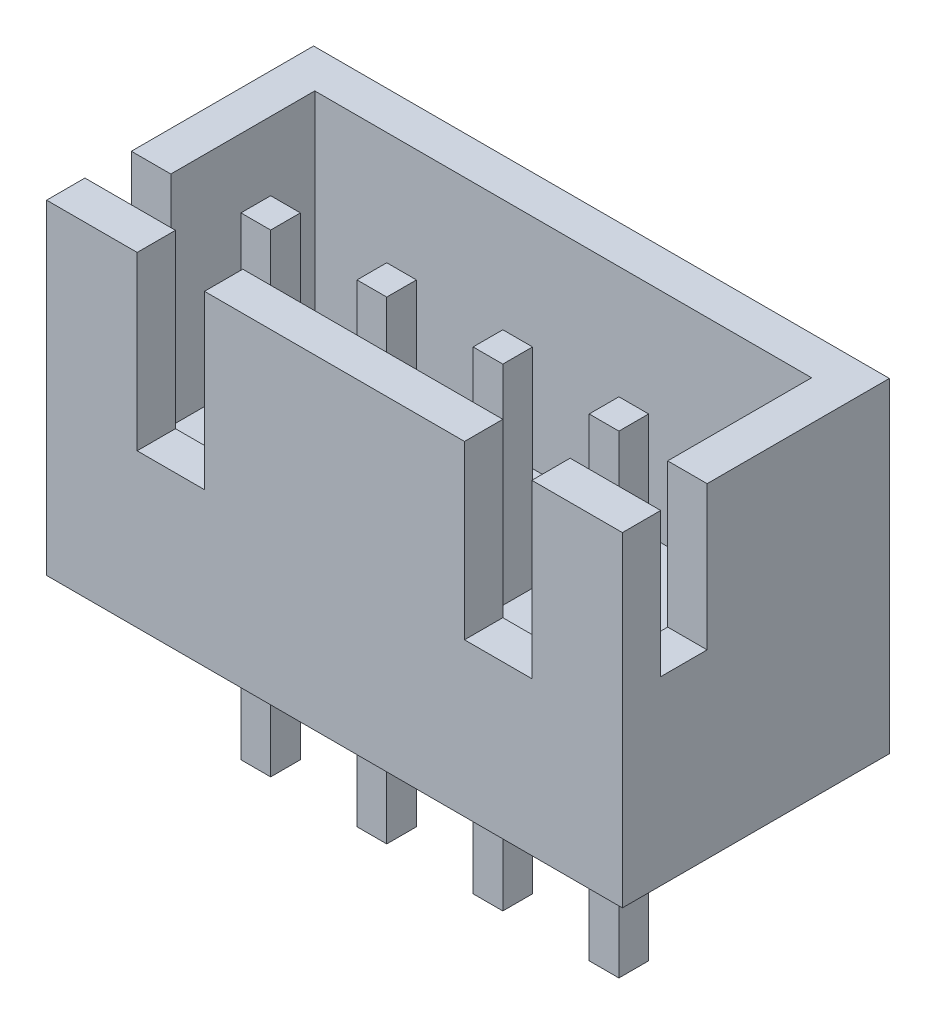
SolidWorks part; units mm, degrees
material "Nylon 101"
ref_plane "Front Plane" through (0, 0, 0) normal (0, 0, 1) x (1, 0, 0)
ref_plane "Top Plane" through (0, 0, 0) normal (0, 1, 0) x (1, 0, 0)
ref_plane "Right Plane" through (0, 0, 0) normal (1, 0, 0) x (0, 0, -1)
ref_plane "Plane1" through (0, 0, 2.875) normal (0, 0, 1) x (1, 0, 0)
sketch "Sketch1" plane through (0, 0, 2.875) normal (0, 0, 1) x (1, 0, 0)
  line L0 (6.2, 7) -> (-6.2, 7)
  line L1 (-6.2, 7) -> (-6.2, 0)
  line L2 (-6.2, 0) -> (6.2, 0)
  line L3 (6.2, 0) -> (6.2, 7)
extrude "Boss-Extrude1" add sketch "Sketch1" against normal blind 5.75
sketch "Sketch2" plane through (-6.2, 0, 0) normal (-1, 0, 0) x (0, 0, 1)
  line L0 (1.05, 7) -> (1.05, 3.9)
  line L1 (1.05, 3.9) -> (2.05, 3.9)
  line L2 (2.05, 3.9) -> (2.05, 7)
  line L3 (2.05, 7) -> (1.05, 7)
extrude "Cut-Extrude1" cut sketch "Sketch2" against normal through all
sketch "Sketch3" plane through (0, 3.9, 0) normal (0, 1, 0) x (-1, 0, 0)
  line L0 (-5.35, 1.05) -> (5.35, 1.05)
  line L1 (5.35, 1.05) -> (5.35, 2.05)
  line L2 (5.35, 2.05) -> (-5.35, 2.05)
  line L3 (-5.35, 2.05) -> (-5.35, 1.05)
extrude "Cut-Extrude2" cut sketch "Sketch3" against normal blind 1.6
sketch "Sketch4" plane through (0, 0, 1.05) normal (0, 0, 1) x (1, 0, 0)
  line L0 (-5.35, 7) -> (-5.35, 2.3)
  line L1 (-5.35, 2.3) -> (5.35, 2.3)
  line L2 (5.35, 2.3) -> (5.35, 7)
  line L3 (5.35, 7) -> (-5.35, 7)
extrude "Cut-Extrude3" cut sketch "Sketch4" against normal blind 3.1
sketch "Sketch5" plane through (0, 0, 2.05) normal (0, 0, -1) x (-1, 0, 0)
  line L0 (-2.8, 7) -> (-4.25, 7)
  line L1 (-4.25, 7) -> (-4.25, 3.3)
  line L2 (-4.25, 3.3) -> (-2.8, 3.3)
  line L3 (-2.8, 3.3) -> (-2.8, 7)
extrude "Cut-Extrude4" cut sketch "Sketch5" against normal through all
sketch "Sketch6" plane through (0, 0, 2.05) normal (0, 0, -1) x (-1, 0, 0)
  line L0 (4.25, 7) -> (2.8, 7)
  line L1 (2.8, 7) -> (2.8, 3.3)
  line L2 (2.8, 3.3) -> (4.25, 3.3)
  line L3 (4.25, 3.3) -> (4.25, 7)
extrude "Cut-Extrude5" cut sketch "Sketch6" against normal through all
sketch "Sketch7" plane through (0, 2.3, 0) normal (0, 1, 0) x (-1, 0, 0)
  line L0 (0.93, 0.82) -> (1.57, 0.82)
  line L1 (1.57, 0.82) -> (1.57, 0.18)
  line L2 (1.57, 0.18) -> (0.93, 0.18)
  line L3 (0.93, 0.18) -> (0.93, 0.82)
extrude "Boss-Extrude2" add sketch "Sketch7" along normal blind 4.5
sketch "Sketch8" plane through (0, 2.3, 0) normal (0, 1, 0) x (-1, 0, 0)
  line L0 (-4.07, 0.82) -> (-3.43, 0.82)
  line L1 (-3.43, 0.82) -> (-3.43, 0.18)
  line L2 (-3.43, 0.18) -> (-4.07, 0.18)
  line L3 (-4.07, 0.18) -> (-4.07, 0.82)
extrude "Boss-Extrude3" add sketch "Sketch8" along normal blind 4.5
sketch "Sketch9" plane through (0, 2.3, 0) normal (0, 1, 0) x (-1, 0, 0)
  line L0 (-1.57, 0.82) -> (-0.93, 0.82)
  line L1 (-0.93, 0.82) -> (-0.93, 0.18)
  line L2 (-0.93, 0.18) -> (-1.57, 0.18)
  line L3 (-1.57, 0.18) -> (-1.57, 0.82)
extrude "Boss-Extrude4" add sketch "Sketch9" along normal blind 4.5
sketch "Sketch10" plane through (0, 2.3, 0) normal (0, 1, 0) x (-1, 0, 0)
  line L0 (3.43, 0.82) -> (4.07, 0.82)
  line L1 (4.07, 0.82) -> (4.07, 0.18)
  line L2 (4.07, 0.18) -> (3.43, 0.18)
  line L3 (3.43, 0.18) -> (3.43, 0.82)
extrude "Boss-Extrude5" add sketch "Sketch10" along normal blind 4.5
sketch "Sketch11" plane through (0, 0, 0) normal (0, -1, 0) x (1, 0, 0)
  line L0 (-0.93, 0.18) -> (-1.57, 0.18)
  line L1 (-1.57, 0.18) -> (-1.57, 0.82)
  line L2 (-1.57, 0.82) -> (-0.93, 0.82)
  line L3 (-0.93, 0.82) -> (-0.93, 0.18)
extrude "Boss-Extrude6" add sketch "Sketch11" along normal blind 3.4
sketch "Sketch12" plane through (0, 0, 0) normal (0, -1, 0) x (1, 0, 0)
  line L0 (4.07, 0.18) -> (3.43, 0.18)
  line L1 (3.43, 0.18) -> (3.43, 0.82)
  line L2 (3.43, 0.82) -> (4.07, 0.82)
  line L3 (4.07, 0.82) -> (4.07, 0.18)
extrude "Boss-Extrude7" add sketch "Sketch12" along normal blind 3.4
sketch "Sketch13" plane through (0, 0, 0) normal (0, -1, 0) x (1, 0, 0)
  line L0 (1.57, 0.18) -> (0.93, 0.18)
  line L1 (0.93, 0.18) -> (0.93, 0.82)
  line L2 (0.93, 0.82) -> (1.57, 0.82)
  line L3 (1.57, 0.82) -> (1.57, 0.18)
extrude "Boss-Extrude8" add sketch "Sketch13" along normal blind 3.4
sketch "Sketch14" plane through (0, 0, 0) normal (0, -1, 0) x (1, 0, 0)
  line L0 (-3.43, 0.18) -> (-4.07, 0.18)
  line L1 (-4.07, 0.18) -> (-4.07, 0.82)
  line L2 (-4.07, 0.82) -> (-3.43, 0.82)
  line L3 (-3.43, 0.82) -> (-3.43, 0.18)
extrude "Boss-Extrude9" add sketch "Sketch14" along normal blind 3.4
ref_point "Point1"
ref_point "Point2"
ref_axis "Axis1" through (-3.75, 6.8, 0.5) along (0, -1, 0)
